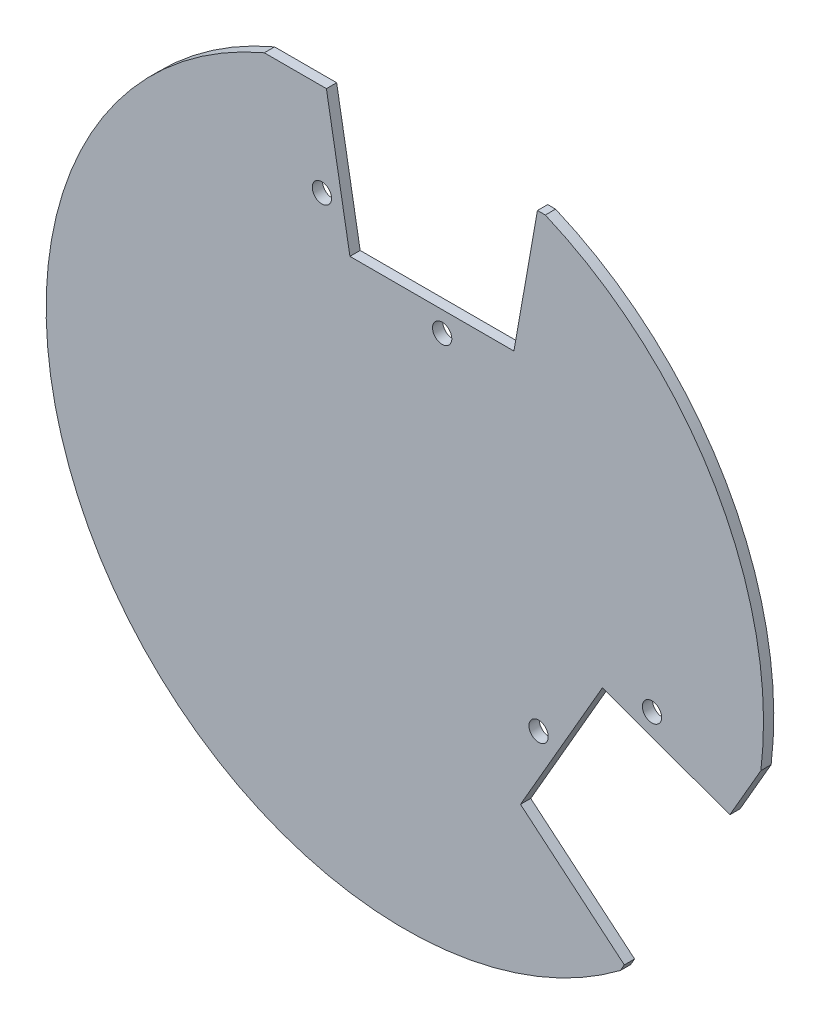
SolidWorks part; units mm, degrees
material "Balsa"
ref_plane "Plan de face" through (0, 0, 0) normal (0, 0, 1) x (1, 0, 0)
ref_plane "Plan de dessus" through (0, 0, 0) normal (0, 1, 0) x (1, 0, 0)
ref_plane "Plan de droite" through (0, 0, 0) normal (1, 0, 0) x (0, 0, -1)
sketch "Esquisse1" plane through (0, 0, 0) normal (0, 0, 1) x (1, 0, 0)
  circle A0 centre (0, 0) radius 175
extrude "Boss.-Extru.1" add sketch "Esquisse1" along normal blind 5
sketch "Esquisse2" plane through (0, 0, 0) normal (0, 0, -1) x (-1, 0, 0)
  line L1 (-13.2204, 90.8876) -> (-13.2204, 0) construction
  line L3 (0, 0) -> (-290.6498, 0) construction
  line L5 (26.7796, 95.8876) -> (38.2633, 161.0152)
  line L6 (38.2633, 161.0152) -> (68.5501, 161.0152)
  line L7 (68.5501, 161.0152) -> (68.5501, 190.2461)
  line L8 (-53.2204, 95.8876) -> (-64.7042, 161.0152)
  line L9 (-64.7042, 161.0152) -> (-94.991, 161.0152)
  line L10 (-94.991, 161.0152) -> (-94.991, 190.2461)
  line L11 (-94.991, 190.2461) -> (68.5501, 190.2461)
  line L12 (26.7796, 95.8876) -> (-53.2204, 95.8876)
  line L13 (-96.4309, -24.752) -> (-158.5749, -47.3706)
  line L14 (-158.5749, -47.3706) -> (-173.7183, -21.1414)
  line L15 (-173.7183, -21.1414) -> (-199.033, -35.7569)
  line L16 (-56.4309, -94.034) -> (-107.0911, -136.543)
  line L17 (-107.0911, -136.543) -> (-91.9477, -162.7722)
  line L18 (-91.9477, -162.7722) -> (-117.2625, -177.3877)
  line L19 (-117.2625, -177.3877) -> (-199.033, -35.7569)
  line L20 (-96.4309, -24.752) -> (-56.4309, -94.034)
  line L21 (-72.1008, -56.893) -> (6.6102, -11.4492) construction
  line L22 (0, 0) -> (87.5, -151.5544) construction
  circle A0 centre (-18.2204, 85.8876) radius 4.7
  circle A1 centre (40.4604, 115.8876) radius 4.7
  circle A2 centre (-65.2706, -58.7232) radius 4.7
  circle A3 centre (-120.5918, -22.9041) radius 4.7
  circle A4 centre (0, 0) radius 175 construction
  point P43 (0, 0)
  dimension "D5" = 9.4
  dimension "D6" = 9.4
  dimension "D1" = 2
  dimension "D2" = 95.8876
  dimension "D3" = 13.2204
  dimension "D4" = 100
  dimension "D7" = 80
  dimension "D8" = 65.1275
extrude "Enlèv. mat.-Extru.1" cut sketch "Esquisse2" against normal blind 5
